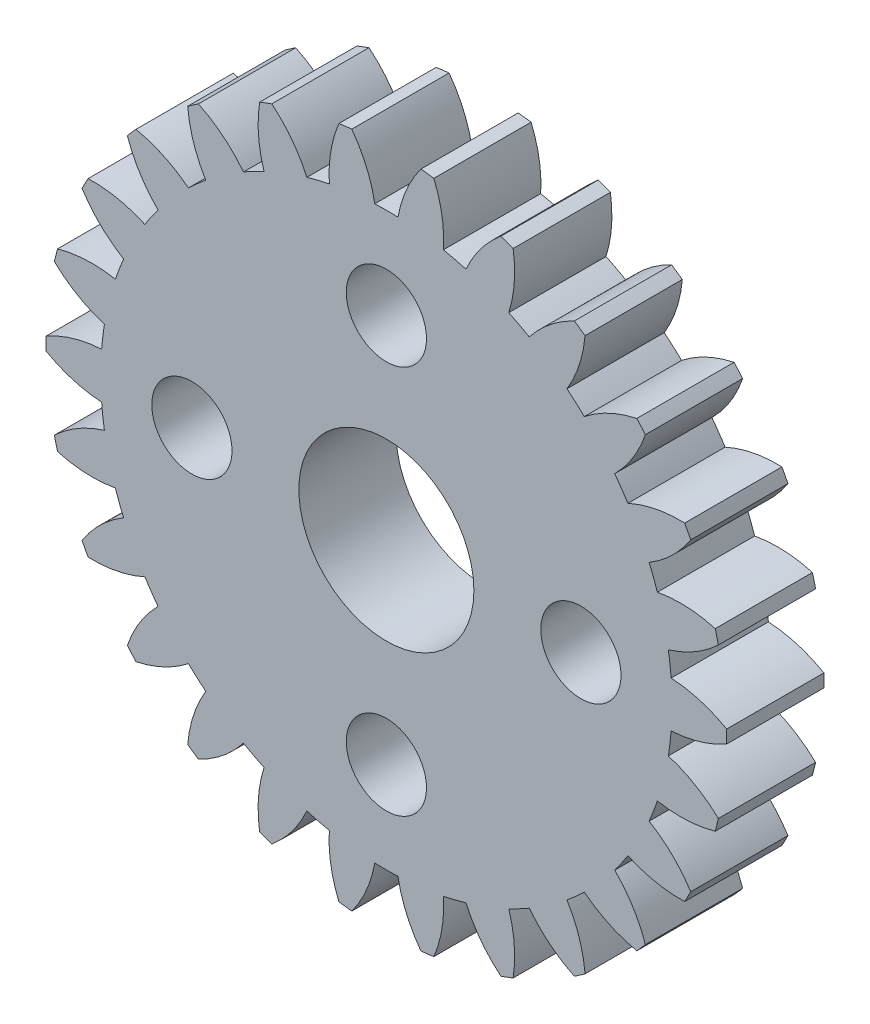
SolidWorks part; units mm, degrees
material "鑄碳鋼"
ref_plane "前基準面" through (0, 0, 0) normal (0, 0, 1) x (1, 0, 0)
ref_plane "上基準面" through (0, 0, 0) normal (0, 1, 0) x (1, 0, 0)
ref_plane "右基準面" through (0, 0, 0) normal (1, 0, 0) x (0, 0, -1)
sketch "草圖1" plane through (0, 0, 0) normal (0, 0, 1) x (1, 0, 0)
  circle A0 centre (0, 0) radius 14
  dimension "D1" = 28
extrude "填料-伸長1" add sketch "草圖1" along normal blind 4
sketch "草圖4" plane through (0, 0, 4) normal (0, 0, 1) x (1, 0, 0)
  line L0 (-1.4216, 13.9276) -> (0, 0) construction
  line L1 (0, 0) -> (1.4216, 13.9276) construction
  line L2 (-0.477, 11.7403) -> (0, 0) construction
  line L3 (0, 0) -> (0.477, 11.7403) construction
  arc A0 (-1.4216, 13.9276) -> (1.4216, 13.9276) centre (0, 0) cw
  circle A1 centre (0, 0) radius 14 construction
  arc A2 (-0.477, 11.7403) -> (0.477, 11.7403) centre (0, 0) cw
  arc A3 (-1.4216, 13.9276) -> (-0.477, 11.7403) centre (-5.5962, 10.8272) cw
  arc A4 (1.4216, 13.9276) -> (0.477, 11.7403) centre (5.5962, 10.8272) ccw
  circle A5 centre (0, 0) radius 13 construction
  point P8 (0, 14)
  point P9 (0, 11.75)
  dimension "D1" = 5.2
  dimension "D2" = 5.2
  dimension "D3" = 11.75
  dimension "D6" = 26
  dimension "D4" = 4.653
  dimension "D5" = 11.656
extrude "除料-伸長1" cut sketch "草圖4" against normal up to next
pattern_circular "環狀複製排列1" count 26 over 360 about axis through (0, 0, 0) along (0, 0, 1) of "除料-伸長1"
sketch "草圖5" plane through (0, 0, 4) normal (0, 0, 1) x (1, 0, 0)
  circle A0 centre (0, 0) radius 3.6
  circle A1 centre (0, 0) radius 8 construction
  circle A2 centre (0, 8) radius 1.65
  circle A3 centre (8, 0) radius 1.65
  circle A4 centre (0, -8) radius 1.65
  circle A5 centre (-8, 0) radius 1.65
  dimension "D1" = 7.2
  dimension "D2" = 16
  dimension "D3" = 3.3
  dimension "D6" = 90
  dimension "D5" = 8
  dimension "D4" = 4
extrude "除料-伸長2" cut sketch "草圖5" against normal up to next
